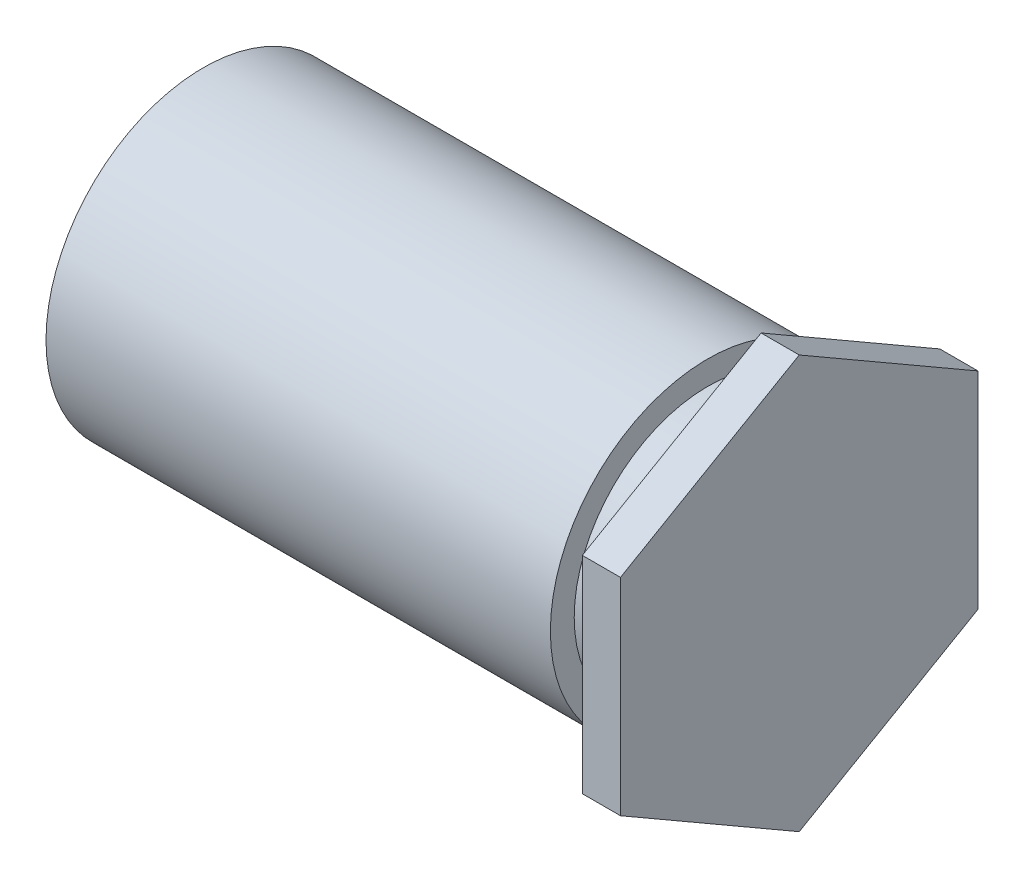
SolidWorks part; units mm, degrees
ref_plane "Front Plane" through (0, 0, 0) normal (0, 0, 1) x (1, 0, 0)
ref_plane "Top Plane" through (0, 0, 0) normal (0, 1, 0) x (1, 0, 0)
ref_plane "Right Plane" through (0, 0, 0) normal (1, 0, 0) x (0, 0, -1)
sketch "Sketch1" plane through (0, 0, 0) normal (0, 0, 1) x (1, 0, 0)
  line L0 (-3.9688, 0) -> (3.9688, 0) construction
  line L1 (-3.9687, 2.0955) -> (-3.9687, -2.0955) construction
  line L2 (0, 1.4224) -> (0, -1.4224) construction
  line L3 (3.9688, 2.3813) -> (3.9688, -2.3813) construction
  line L4 (0, 1.4224) -> (-3.9687, 1.4224) construction
  line L5 (0, -1.4224) -> (-3.9687, -1.4224) construction
  point P4 (0, 0)
  point P10 (3.4608, 0)
  point P11 (2.7496, 0)
  dimension "OD" = 4.191
  dimension "Length" = 7.9375
  dimension "Thread Height" = 3.9688
  dimension "Thread Size" = 2.8448
  dimension "D1" = 4.7625
  dimension "D3" = 0.7112
  dimension "D4" = 0.508
ref_plane "Plane1" through (-3.9687, 0, 0) normal (1, 0, 0) x (0, 0, -1)
sketch "Sketch2" plane through (-3.9687, 0, 0) normal (1, 0, 0) x (0, 0, -1)
  circle A0 centre (0, 0) radius 2.0955
extrude "Extrude1" add sketch "Sketch2" along normal up to vertex (7.9375 mm away) up to point (3.9688, 0, 0)
sketch "Sketch3" plane through (3.9688, 0, 0) normal (1, 0, 0) x (0, 0, -1)
  line L1 (0, 2.7496) -> (-2.3813, 1.3748)
  line L2 (-2.3813, 1.3748) -> (-2.3813, -1.3748)
  line L3 (-2.3813, -1.3748) -> (0, -2.7496)
  line L4 (0, -2.7496) -> (2.3813, -1.3748)
  line L5 (2.3813, -1.3748) -> (2.3813, 1.3748)
  line L6 (2.3813, 1.3748) -> (0, 2.7496)
  circle A0 centre (0, 0) radius 2.3813 construction
extrude "Extrude2" add sketch "Sketch3" against normal up to vertex (0.508 mm away) up to point (3.4608, 0, 0)
sketch "Sketch4" plane through (3.4608, 0, 0) normal (-1, 0, 0) x (0, 0, 1)
  circle A0 centre (0, 0) radius 1.778
  circle A1 centre (0, 0) radius 2.0955 construction
  circle A2 centre (0, 0) radius 2.0955
  dimension "D1" = 0.3175
extrude "Extrude3" cut sketch "Sketch4" along normal up to vertex (0.7112 mm away) up to point (2.7496, 0, 0)
sketch "Sketch5" plane through (-3.9687, 0, 0) normal (-1, 0, 0) x (0, 0, 1)
  line L0 (0, 0) -> (-1.0058, 1.0058) construction
  line L1 (0, 0) -> (-1.4224, 0) construction
  circle A0 centre (0, 0) radius 1.4224
  dimension "D1" = 45
extrude "Extrude4" cut sketch "Sketch5" against normal up to vertex (3.9688 mm away) up to point (0, 0, 0)
sketch "Sketch6" plane through (-3.9687, 0, 0) normal (-1, 0, 0) x (0, 0, 1)
  circle A1 centre (0, 0) radius 1.4224
  circle A2 centre (0, 0) radius 1.4224
  dimension "D1" = 0
curve "Helix/Spiral1" pitch 0.635 height 3.9688 turns 6.25 parameters "Pitch"=0.635
sketch "Sketch7" plane through (0, 0, 0) normal (0, 0, 1) x (1, 0, 0)
  line L0 (-4.5244, 1.4224) -> (-3.9687, 1.4224)
  line L1 (-4.5244, 1.4224) -> (-4.2862, 1.01)
  line L2 (-4.2862, 1.01) -> (-4.2069, 1.01)
  line L3 (-4.2069, 1.01) -> (-3.9687, 1.4224)
  line L4 (-4.2466, 1.01) -> (-4.2466, 1.4224) construction
  line L5 (-4.4053, 1.2162) -> (-4.0878, 1.2162) construction
  dimension "D1" = 60
  dimension "D2" = 0.0794
sweep "Sweep1" add profiles "Sketch7" path "Helix/Spiral1"
sketch "Sketch8" plane through (-3.9687, 0, 0) normal (-1, 0, 0) x (0, 0, 1)
  circle A2 centre (0, 0) radius 1.4732
  circle A3 centre (0, 0) radius 1.4732
  dimension "D1" = 0.0508
extrude "Extrude6" cut sketch "Sketch8" along normal through all and the other way through all draft 45
equation "\"D2@Sketch7\" = \"Pitch@Helix/Spiral1\"*.125"
equation "\"D3@Sketch7\" = \"Pitch@Helix/Spiral1\"*.5"
equation "\"D3@Helix/Spiral1\" = \"Thread Height@Sketch1\""
